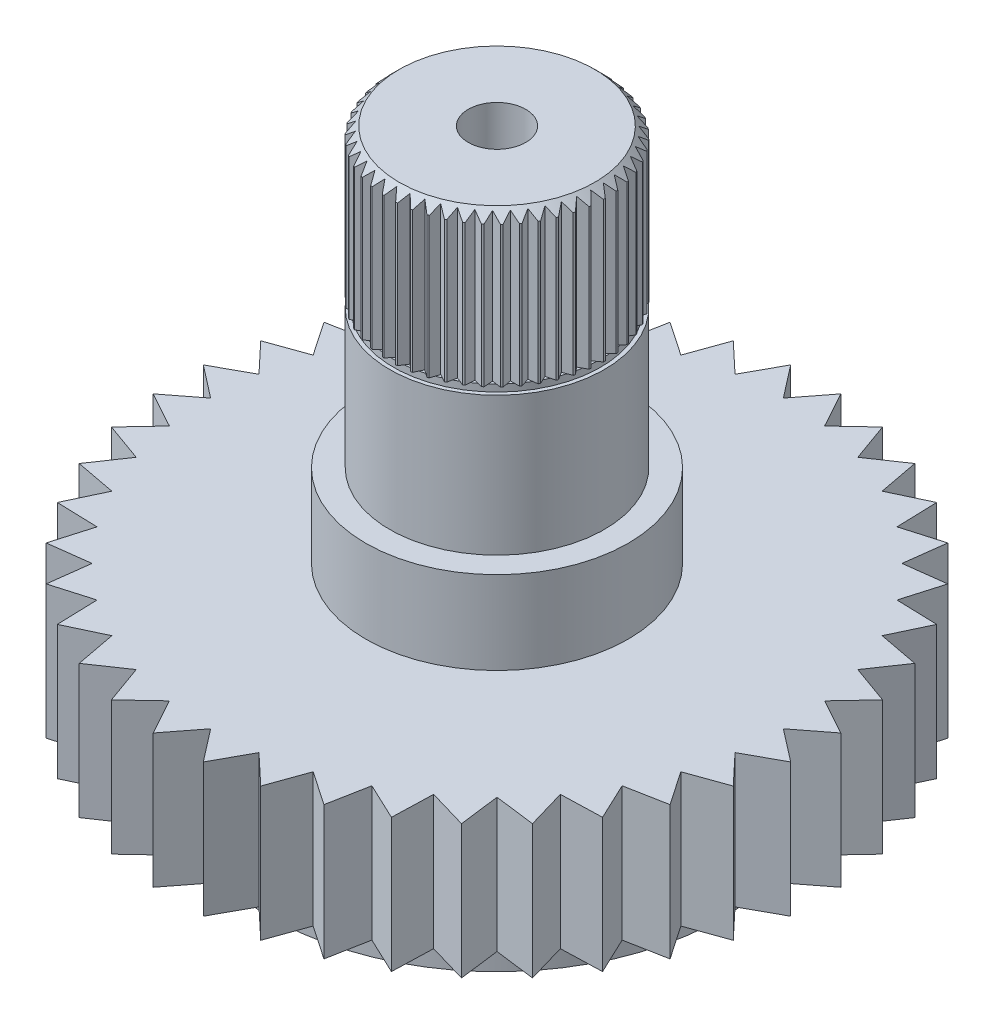
SolidWorks part; units mm, degrees
material "Nailon 6/10"
ref_plane "Front Plane" through (0, 0, 0) normal (0, 0, 1) x (1, 0, 0)
ref_plane "Top Plane" through (0, 0, 0) normal (0, 1, 0) x (1, 0, 0)
ref_plane "Right Plane" through (0, 0, 0) normal (1, 0, 0) x (0, 0, -1)
sketch "Sketch1" plane through (0, 0, 0) normal (0, 0, 1) x (1, 0, 0)
  line L0 (0, 0) -> (0, 35.5657) construction
  line L1 (6.016, 0) -> (8.509, 0)
  line L2 (8.509, 0) -> (8.509, 3.556)
  line L3 (8.509, 3.556) -> (3.4925, 3.556)
  line L4 (2.8575, 5.7658) -> (2.8575, 9.4521)
  line L5 (2.8575, 13.6398) -> (0, 13.6398)
  line L6 (0, 13.6398) -> (0, 0.9398)
  line L7 (0, 0.9398) -> (5, 0.9398)
  line L8 (5, 0.9398) -> (5, -1.6002)
  line L9 (2.8575, 9.6398) -> (2.7555, 9.6398)
  line L10 (2.7555, 9.6398) -> (2.7555, 9.4521)
  line L11 (2.7555, 9.4521) -> (2.8575, 9.4521)
  line L12 (2.8575, 9.6398) -> (2.8575, 13.6398)
  line L13 (2.8575, 5.7658) -> (3.4925, 5.7658)
  line L14 (3.4925, 5.7658) -> (3.4925, 3.556)
  line L15 (6.016, 0) -> (6.016, -1.6002)
  line L16 (6.016, -1.6002) -> (5, -1.6002)
  dimension "D1" = 5.715
  dimension "D2" = 10
  dimension "D3" = 17.018
  dimension "D4" = 3.556
  dimension "D5" = 15.24
  dimension "D6" = 2.54
  dimension "D7" = 7.366
  dimension "D8" = 6.985
  dimension "D9" = 1.6002
  dimension "D10" = 1.016
  dimension "D11" = 4
revolve "Revolve1" add sketch "Sketch1" angle 360 about L0
sketch "Sketch2" plane through (0, 0.9398, 0) normal (0, -1, 0) x (1, 0, 0)
  line L0 (0, 1.5875) -> (0, -1.5875)
  arc A0 (0, 1.5875) -> (0, -1.5875) centre (0, 0) cw
  dimension "D1" = 1.5875
extrude "Cut-Extrude1" cut sketch "Sketch2" against normal blind 2.032
sketch "Sketch3" plane through (0, 3.556, 0) normal (0, 1, 0) x (-1, 0, 0)
  line L0 (0.6676, -8.4828) -> (0, -7.62)
  line L1 (0, -7.62) -> (-0.6676, -8.4828)
  line L2 (-0.6676, -8.4828) -> (-1.192, -7.5262) construction
  line L3 (-1.192, -7.5262) -> (0, 0) construction
  line L4 (0, 0) -> (-0.6676, -8.4828) construction
  line L5 (0, -7.62) -> (0, 0) construction
  circle A0 centre (0, 0) radius 8.509 construction
  arc A1 (-0.6676, -8.4828) -> (0.6676, -8.4828) centre (0, 0) ccw
  circle A2 centre (0, 0) radius 7.62 construction
  dimension "D1" = 9
extrude "Cut-Extrude2" cut sketch "Sketch3" against normal through all
pattern_circular "CirPattern1" count 40 over 360 about axis through (0, 0, 0) along (0, 1, 0) of "Cut-Extrude2"
chamfer "Chamfer1" distance 0.254 angle 45 1 edges at (0, 13.6398, -2.8575)
sketch "Sketch4" plane through (0, 13.6398, 0) normal (0, 1, 0) x (-1, 0, 0)
  line L0 (0.1555, -2.8533) -> (0, -2.667)
  line L1 (0, -2.667) -> (-0.1555, -2.8533)
  line L2 (-0.1555, -2.8533) -> (-0.2898, -2.6512) construction
  line L3 (-0.2898, -2.6512) -> (0, 0) construction
  line L4 (0, 0) -> (-0.1555, -2.8533) construction
  line L5 (0, -2.667) -> (0, 0) construction
  circle A0 centre (0, 0) radius 2.8575 construction
  circle A1 centre (0, 0) radius 2.667 construction
  arc A2 (-0.1555, -2.8533) -> (0.1555, -2.8533) centre (0, 0) ccw
  dimension "D2" = 5.334
  dimension "D1" = 6.238
extrude "Cut-Extrude3" cut sketch "Sketch4" against normal up to surface (4 mm away) up to face at (0, 9.6398, -2.8575)
pattern_circular "CirPattern2" count 50 over 360 about axis through (0, 0, 0) along (0, 1, 0) of "Cut-Extrude3"
ref_axis "Axis1" through (0, -31.0516, 0) along (0, 1, 0)
sketch "Croquis1" plane through (0, 13.6398, 0) normal (0, 1, 0) x (1, 0, 0)
  circle A0 centre (0, 0) radius 0.765
  dimension "D1" = 1.53
extrude "Cortar-Extruir1" cut sketch "Croquis1" against normal blind 2.54
equation "\"D1@Sketch3\"=360/\"D1@CirPattern1\""
